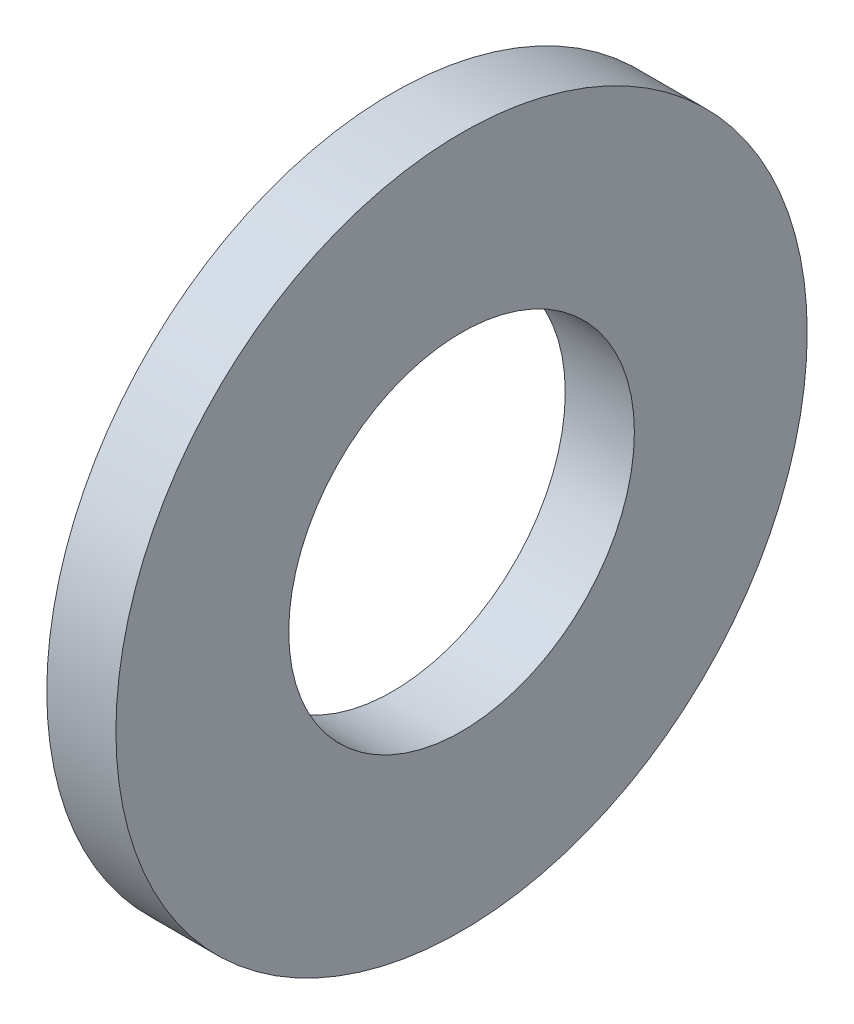
SolidWorks part; units mm, degrees
ref_plane "Front Plane" through (0, 0, 0) normal (0, 0, 1) x (1, 0, 0)
ref_plane "Top Plane" through (0, 0, 0) normal (0, 1, 0) x (1, 0, 0)
ref_plane "Right Plane" through (0, 0, 0) normal (1, 0, 0) x (0, 0, -1)
ref_axis "Axis_X" through (-0.05, 0, 0) along (1, 0, 0)
ref_axis "Axis_Y" through (0, 5.5, 0) along (0, -1, 0)
ref_axis "Axis_Z" through (0, 0, -5.5) along (0, 0, 1)
sketch "Sketch1" plane through (0, 0, 0) normal (0, 0, 1) x (1, 0, 0)
  line L0 (0, 5) -> (0, 2.5)
  line L1 (1, 2.5) -> (1, 5)
  line L3 (0, 5) -> (1, 5)
  line L7 (0, 2.5) -> (1, 2.5)
  dimension "FIX_51" = 1
  dimension "FIX_52" = 2.5
  dimension "FIX_53" = 5
revolve "Revolve1" add sketch "Sketch1" angle 360 about axis through (-0.05, 0, 0) along (1, 0, 0)
equation "\"Factor\"= 1.082532"
